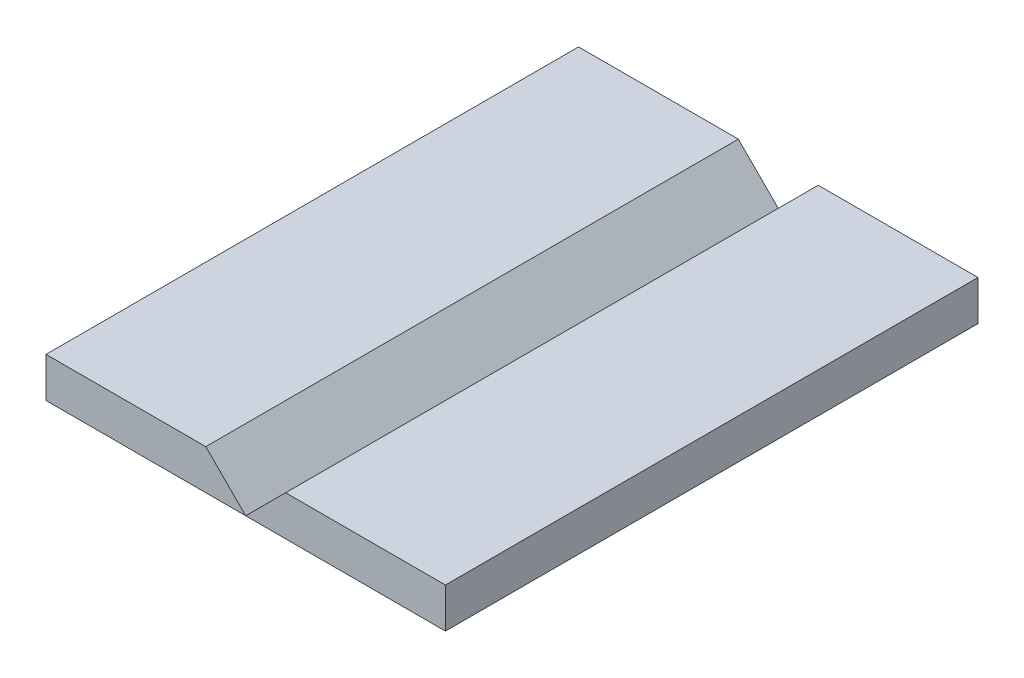
SolidWorks part; units mm, degrees
ref_plane "Front Plane" through (0, 0, 0) normal (0, 0, 1) x (1, 0, 0)
ref_plane "Top Plane" through (0, 0, 0) normal (0, 1, 0) x (1, 0, 0)
ref_plane "Right Plane" through (0, 0, 0) normal (1, 0, 0) x (0, 0, -1)
sketch "Sketch1" plane through (0, 0, 0) normal (0, 0, 1) x (1, 0, 0)
  line L0 (75, 0) -> (75, 15) construction
  line L1 (0, 0) -> (150, 0)
  line L2 (0, 0) -> (0, 15)
  line L3 (0, 15) -> (60, 15)
  line L5 (75, 0) -> (60, 15)
  line L6 (150, 0) -> (150, 15)
  line L7 (150, 15) -> (90, 15)
  line L8 (75, 0) -> (90, 15)
extrude "Boss-Extrude1" add sketch "Sketch1" along normal blind 200 contours L1 L5 L3 L2 | L8 L1 L6 L7 region at (33.8889, 7.2222, 0) region at (116.1111, 7.2222, 0)
